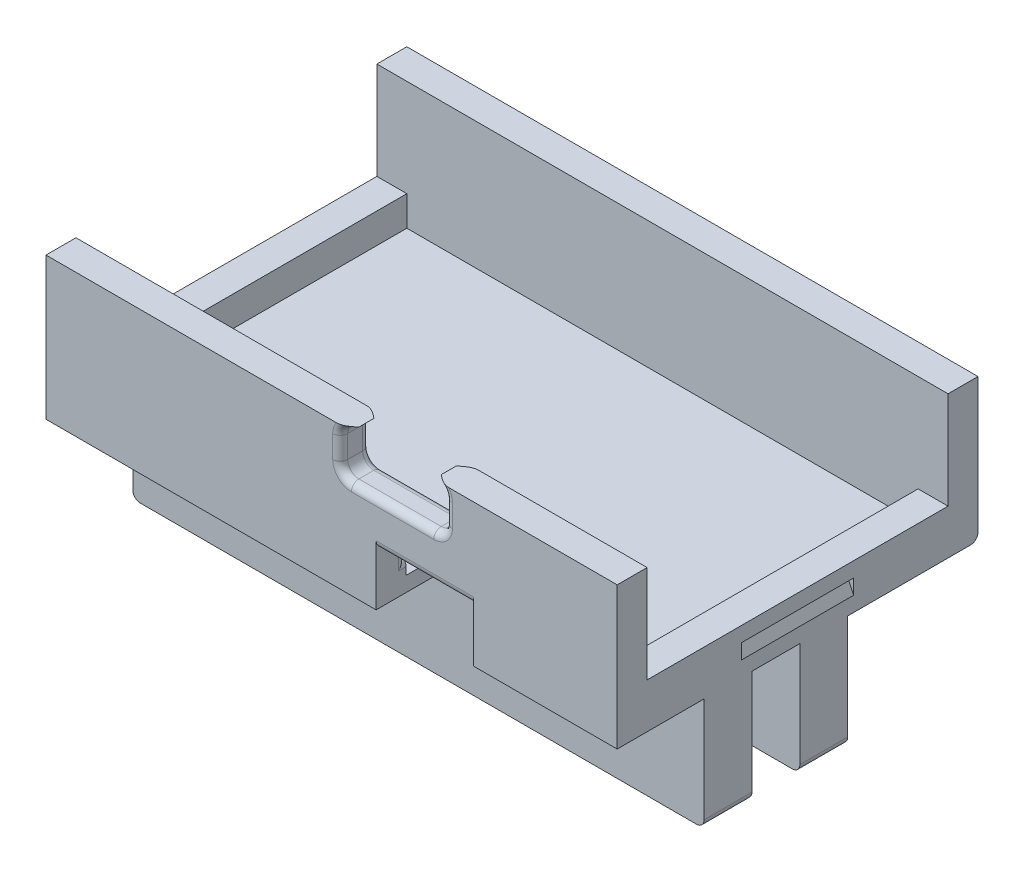
SolidWorks part; units mm, degrees
ref_plane "Alzado" through (0, 0, 0) normal (0, 0, 1) x (1, 0, 0)
ref_plane "Planta" through (0, 0, 0) normal (0, 1, 0) x (1, 0, 0)
ref_plane "Vista lateral" through (0, 0, 0) normal (1, 0, 0) x (0, 0, -1)
sketch "Sketch1" plane through (0, 0, 0) normal (0, 1, 0) x (1, 0, 0)
  line L1 (-34.15, -20.1) -> (34.15, -20.1)
  line L2 (-34.15, -20.1) -> (-34.15, 20.1)
  line L3 (-34.15, 20.1) -> (34.15, 20.1)
  line L4 (34.15, -20.1) -> (34.15, 20.1)
  line L5 (-34.15, -20.1) -> (34.15, 20.1) construction
  line L6 (-34.15, 20.1) -> (34.15, -20.1) construction
  point P0 (0, 0)
  dimension "D1" = 68.3
  dimension "D2" = 40.2
sketch "Sketch2" plane through (0, 0, 0) normal (0, 1, 0) x (1, 0, 0)
  line L8 (-38.15, 24.1) -> (-38.15, -24.1)
  line L9 (-38.15, -24.1) -> (38.15, -24.1)
  line L10 (38.15, -24.1) -> (38.15, 24.1)
  line L11 (38.15, 24.1) -> (-38.15, 24.1)
  line L12 (-38.15, 24.1) -> (-38.15, -24.1)
  line L13 (-38.15, -24.1) -> (38.15, -24.1)
  line L14 (38.15, -24.1) -> (38.15, 24.1)
  line L15 (38.15, 24.1) -> (-38.15, 24.1)
  dimension "D1" = 4
extrude "Boss-Extrude1" add sketch "Sketch2" along normal blind 4
sketch "Sketch3" plane through (0, 4, 0) normal (0, 1, 0) x (1, 0, 0)
  line L4 (-34.15, -20.1) -> (34.15, -20.1) construction
  line L6 (-34.15, 20.1) -> (34.15, 20.1) construction
  line L8 (38.15, 24.1) -> (-38.15, 24.1)
  line L9 (-38.15, 24.1) -> (-38.15, -24.1)
  line L10 (-38.15, -24.1) -> (38.15, -24.1)
  line L11 (38.15, -24.1) -> (38.15, 24.1)
  line L12 (38.15, 24.1) -> (-38.15, 24.1)
  line L14 (-38.15, -24.1) -> (38.15, -24.1)
  line L16 (-34.15, -20.1) -> (34.15, -20.1)
  line L18 (-34.15, 20.1) -> (34.15, 20.1)
  line L20 (-34.15, 20.1) -> (-38.15, 20.1)
  line L21 (-38.15, 24.1) -> (-38.15, -24.1) construction
  line L22 (-38.15, 20.1) -> (-38.15, 24.1)
  line L23 (34.15, 20.1) -> (38.15, 20.1)
  line L24 (38.15, -24.1) -> (38.15, 24.1) construction
  line L25 (38.15, 20.1) -> (38.15, 24.1)
  line L26 (34.15, -20.1) -> (38.15, -20.1)
  line L27 (38.15, -20.1) -> (38.15, -24.1)
  line L28 (-34.15, -20.1) -> (-38.15, -20.1)
  line L29 (-38.15, -20.1) -> (-38.15, -24.1)
  dimension "D1" = 0
extrude "Boss-Extrude2" add sketch "Sketch3" along normal blind 15
sketch "Sketch10" plane through (0, 4, 0) normal (0, 1, 0) x (1, 0, 0)
  line L0 (-38.15, 20.1) -> (-34.15, 20.1)
  line L1 (-34.15, 20.1) -> (-34.15, -20.1)
  line L2 (-34.15, -20.1) -> (-38.15, -20.1)
  line L3 (-38.15, -20.1) -> (-38.15, 20.1)
  line L4 (34.15, 20.1) -> (38.15, 20.1)
  line L5 (38.15, 20.1) -> (38.15, -20.1)
  line L6 (38.15, -20.1) -> (34.15, -20.1)
  line L7 (34.15, -20.1) -> (34.15, 20.1)
extrude "Boss-Extrude5" add sketch "Sketch10" along normal blind 2
sketch "Sketch5" plane through (0, 4, 0) normal (0, 1, 0) x (1, 0, 0)
  line L1 (18.95, -12.9) -> (18.95, -24.1)
  line L3 (-38.15, -24.1) -> (38.15, -24.1) construction
  line L4 (18.95, -24.1) -> (5.95, -24.1)
  line L5 (5.95, -24.1) -> (5.95, -12.9)
  line L6 (5.95, -12.9) -> (18.95, -12.9)
  line L7 (34.15, -20.1) -> (34.15, 20.1) construction
  line L8 (-34.15, -20.1) -> (34.15, -20.1) construction
  dimension "D1" = 15.2
  dimension "D2" = 13
  dimension "D3" = 7.2
extrude "Cut-Extrude1" cut sketch "Sketch5" against normal blind 4 and the other way blind 3
sketch "Sketch7" plane through (38.15, 0, 0) normal (1, 0, 0) x (0, 0, -1)
  line L0 (-20.1, 12.5) -> (-20.1, 17)
  line L2 (-20.1, 12.5) -> (-17.1, 17)
  line L3 (-17.1, 17) -> (-20.1, 17)
  line L4 (-20.1, 19) -> (-20.1, 6) construction
  line L5 (-20.1, 4) -> (20.1, 4) construction
  dimension "D1" = 3
  dimension "D2" = 13
  dimension "D3" = 4.5
sketch "Sketch8" plane through (0, 0, 24.1) normal (0, 0, 1) x (1, 0, 0)
  line L0 (2.65, 19) -> (13.65, 19)
  line L2 (15.15, 17.5) -> (15.15, 14.5)
  line L3 (13.65, 13) -> (2.65, 13)
  line L4 (1.15, 14.5) -> (1.15, 17.5)
  line L7 (5.95, 4) -> (18.95, 4) construction
  arc A0 (13.65, 19) -> (15.15, 17.5) centre (13.65, 17.5) cw
  arc A1 (15.15, 14.5) -> (13.65, 13) centre (13.65, 14.5) cw
  arc A2 (2.65, 13) -> (1.15, 14.5) centre (2.65, 14.5) cw
  arc A3 (1.15, 17.5) -> (2.65, 19) centre (2.65, 17.5) cw
  dimension "D1" = 6
  dimension "D4" = 1.5
  dimension "D2" = 15
  dimension "D3" = 14
  dimension "D5" = 19
extrude "Cut-Extrude2" cut sketch "Sketch8" against normal up to next
sketch "Sketch14" plane through (38.15, 0, 0) normal (1, 0, 0) x (0, 0, -1)
  line L0 (-20.1, 6) -> (20.1, 6) construction
  line L2 (-20.1, 19) -> (-20.1, 6) construction
  point P3 (0, 6)
sketch "Sketch13" plane through (0, 0, 0) normal (0, 0, 1) x (1, 0, 0)
  line L0 (38.15, 0) -> (38.15, 6) construction
  line L2 (38.15, 4) -> (37.15, 4)
  line L3 (37.15, 4) -> (38.15, 2)
  line L4 (38.15, 4) -> (38.15, 2) construction
  line L5 (38.15, 4) -> (38.15, 2)
  point P9 (38.15, 3)
  point P13 (38.15, 3)
  dimension "D1" = 1
  dimension "D2" = 2
extrude "Cut-Extrude3" cut sketch "Sketch13" against normal mid plane 15
mirror "Mirror2" about plane through (0, 0, 0) normal (1, 0, 0) of "Cut-Extrude3"
fillet "Fillet3" radius 1 1 edges at (0, 0, -24.1)
sketch "Sketch17" plane through (0, 0, 0) normal (0, -1, 0) x (1, 0, 0)
  line L0 (38.15, 20.1) -> (38.15, -20.1) construction
  line L1 (-38.15, 24.1) -> (38.15, 24.1)
  line L2 (-38.15, 24.1) -> (-38.15, 16.1)
  line L3 (-38.15, 16.1) -> (38.15, 16.1)
  line L4 (38.15, 24.1) -> (38.15, 16.1)
  line L5 (-38.15, 24.1) -> (38.15, 16.1) construction
  line L6 (-38.15, 16.1) -> (38.15, 24.1) construction
  line L7 (-38.15, -23.1) -> (-38.15, 24.1) construction
  line L8 (-38.15, 9.7) -> (38.15, 9.7)
  line L9 (-38.15, 9.7) -> (-38.15, 3.7)
  line L10 (-38.15, 3.7) -> (38.15, 3.7)
  line L11 (38.15, 9.7) -> (38.15, 3.7)
  line L12 (-38.15, 9.7) -> (38.15, 3.7) construction
  line L13 (-38.15, 3.7) -> (38.15, 9.7) construction
  line L14 (38.15, 24.1) -> (38.15, -23.1) construction
  point P4 (0, 20.1)
  point P12 (0, 6.7)
  dimension "D1" = 8
  dimension "D2" = 6
  dimension "D3" = 6.4
extrude "Boss-Extrude6" add sketch "Sketch17" along normal blind 15
ref_plane "Plane1" through (0, 0, 0) normal (0, -1, 0) x (-1, 0, 0)
sketch "Sketch20" plane through (0, 0, 24.1) normal (0, 0, 1) x (1, 0, 0)
  line L0 (0, 0) -> (0, -15) construction
  line L1 (18.95, 7) -> (18.95, 0) construction
  line L2 (38.15, -15) -> (-38.15, -15) construction
  line L3 (-3.575, 0) -> (3.575, 0) construction
  circle A0 centre (23.95, -9) radius 2.55
  circle A1 centre (-23.95, -9) radius 2.55
  point P8 (18.95, 3.5)
  dimension "D1" = 5.1
  dimension "D2" = 6.45
  dimension "D3" = 5
extrude "Cut-Extrude5" cut sketch "Sketch20" against normal through all
fillet "Fillet4" radius 1 4 edges at (-38.15, -15, 6.7) (-38.15, -15, 20.1) (38.15, -15, 6.7) (38.15, -15, 20.1)
fillet "Fillet5" radius 1 21 edges at (12.45, 4, 12.9) (5.95, 4, 16.5) (18.95, 4, 16.5) (18.95, 5.5, 20.1) (5.95, 5.5, 20.1) (12.45, 7, 20.1) (12.45, 7, 24.1) (1.5893, 18.5607, 24.1) (14.7107, 18.5607, 24.1) (15.15, 16, 24.1) (14.7107, 13.4393, 24.1) (8.15, 13, 24.1) (1.5893, 13.4393, 24.1) (14.7107, 13.4393, 20.1) (15.15, 16, 20.1) (14.7107, 18.5607, 20.1) (1.5893, 18.5607, 20.1) (1.15, 16, 20.1) (1.5893, 13.4393, 20.1) (1.15, 16, 24.1) (8.15, 13, 20.1)
sketch "Sketch21" plane through (0, 4, 0) normal (0, 1, 0) x (1, 0, 0)
  line L1 (-34.15, 20.1) -> (34.15, 20.1)
  line L2 (-34.15, 20.1) -> (-34.15, -20.1)
  line L3 (-34.15, -20.1) -> (34.15, -20.1)
  line L4 (34.15, 20.1) -> (34.15, -20.1)
  line L5 (-34.15, 20.1) -> (34.15, -20.1) construction
  line L6 (-34.15, -20.1) -> (34.15, 20.1) construction
  point P4 (0, 0)
extrude "Cut-Extrude6" cut sketch "Sketch21" against normal blind 2
ref_plane "Plane2" through (0, 0, 34.1) normal (0, 0, 1) x (1, 0, 0)
mirror "Mirror4" [suppressed] about plane through (0, 0, 34.1) normal (0, 0, 1) of bodies 114
sketch "Sketch22" [suppressed] plane through (0, 0, 34.1) normal (0, 0, 1) x (1, 0, 0)
  line L0 (-37.15, -15) -> (37.15, -15) construction
  line L1 (-38.15, 19) -> (38.15, 19)
  line L2 (-38.15, 19) -> (-38.15, -15)
  line L3 (-38.15, -15) -> (38.15, -15)
  line L4 (38.15, 19) -> (38.15, -15)
  line L5 (-38.15, 19) -> (38.15, -15) construction
  line L6 (-38.15, -15) -> (38.15, 19) construction
  line L7 (38.15, -14) -> (38.15, 0) construction
  point P4 (0, 2)
extrude "Cut-Extrude7" [suppressed] cut sketch "Sketch22" against normal through all
sketch "Sketch23" [suppressed] plane through (0, 0, 24.1) normal (0, 0, 1) x (1, 0, 0)
  line L0 (-35.55, 0) -> (35.55, 0) construction
  line L1 (-3.575, 0) -> (3.575, 0) construction
  line L3 (-35.55, 0) -> (-41.9, 0)
  line L4 (-35.55, 0) -> (-35.55, -14)
  line L5 (-35.55, -14) -> (-41.9, -14)
  line L6 (-41.9, 0) -> (-41.9, -14)
  line L7 (-35.55, 0) -> (-41.9, -14) construction
  line L8 (-35.55, -14) -> (-41.9, 0) construction
  line L9 (35.55, 0) -> (41.9, 0)
  line L10 (35.55, 0) -> (35.55, -14)
  line L11 (35.55, -14) -> (41.9, -14)
  line L12 (41.9, 0) -> (41.9, -14)
  line L13 (35.55, 0) -> (41.9, -14) construction
  line L14 (35.55, -14) -> (41.9, 0) construction
  line L15 (29.05, 0) -> (22.7, 0)
  line L16 (29.05, 0) -> (29.05, -14)
  line L17 (29.05, -14) -> (22.7, -14)
  line L18 (22.7, 0) -> (22.7, -14)
  line L19 (29.05, 0) -> (22.7, -14) construction
  line L20 (29.05, -14) -> (22.7, 0) construction
  line L21 (-22.7, 0) -> (-29.05, 0)
  line L22 (-22.7, 0) -> (-22.7, -14)
  line L23 (-22.7, -14) -> (-29.05, -14)
  line L24 (-29.05, 0) -> (-29.05, -14)
  line L25 (-22.7, 0) -> (-29.05, -14) construction
  line L26 (-22.7, -14) -> (-29.05, 0) construction
  point P6 (0, 0)
  point P10 (-38.725, -7)
  point P14 (38.725, -7)
  point P19 (25.875, -7)
  point P24 (-25.875, -7)
  dimension "D1" = 71.1
  dimension "D2" = 6.35
  dimension "D3" = 14
  dimension "D4" = 6.5
  dimension "D5" = 6.5
  dimension "D6" = 6.35
extrude "Boss-Extrude7" [suppressed] add sketch "Sketch23" against normal through all
sketch "Sketch24" [suppressed] plane through (0, 0, 64.5) normal (0, 0, 1) x (1, 0, 0)
  line L4 (-37.15, -15) -> (37.15, -15)
  line L5 (38.15, -14) -> (38.15, 0)
  line L6 (38.15, 0) -> (-38.15, 0)
  line L7 (-38.15, 0) -> (-38.15, -14)
  line L8 (-37.15, -15) -> (37.15, -15)
  line L9 (38.15, -14) -> (38.15, 0)
  line L10 (38.15, 0) -> (-38.15, 0)
  line L11 (-38.15, 0) -> (-38.15, -14)
  circle A0 centre (22.95, -9) radius 2.55 construction
  circle A1 centre (22.95, -9) radius 2.55
  arc A2 (37.15, -15) -> (38.15, -14) centre (37.15, -14) ccw
  arc A3 (-38.15, -14) -> (-37.15, -15) centre (-37.15, -14) ccw
  arc A4 (37.15, -15) -> (38.15, -14) centre (37.15, -14) ccw
  arc A5 (-38.15, -14) -> (-37.15, -15) centre (-37.15, -14) ccw
  dimension "D1" = 0
extrude "Boss-Extrude8" [suppressed] add sketch "Sketch24" along normal blind 10 and the other way blind 15
sketch "Sketch25" [suppressed] plane through (0, 0, 74.5) normal (0, 0, 1) x (1, 0, 0)
  line L4 (-37.15, -15) -> (37.15, -15)
  line L5 (38.15, -14) -> (38.15, 0)
  line L6 (38.15, 0) -> (-38.15, 0)
  line L7 (-38.15, 0) -> (-38.15, -14)
  line L8 (-37.15, -15) -> (37.15, -15)
  line L9 (38.15, -14) -> (38.15, 0)
  line L10 (38.15, 0) -> (-38.15, 0)
  line L11 (-38.15, 0) -> (-38.15, -14)
  circle A0 centre (22.95, -9) radius 2.55 construction
  circle A1 centre (22.95, -9) radius 2.55
  arc A2 (-38.15, -14) -> (-37.15, -15) centre (-37.15, -14) ccw
  arc A3 (37.15, -15) -> (38.15, -14) centre (37.15, -14) ccw
  arc A4 (-38.15, -14) -> (-37.15, -15) centre (-37.15, -14) ccw
  arc A5 (37.15, -15) -> (38.15, -14) centre (37.15, -14) ccw
  dimension "D1" = 0
extrude "Cut-Extrude10" [suppressed] cut sketch "Sketch25" against normal blind 6.4 from offset 6.35 offset against normal yes
sketch "Sketch27" [suppressed] plane through (0, 0, 61.75) normal (0, 0, 1) x (1, 0, 0)
  line L4 (-37.15, -15) -> (37.15, -15)
  line L5 (38.15, -14) -> (38.15, 0)
  line L6 (38.15, 0) -> (-38.15, 0)
  line L7 (-38.15, 0) -> (-38.15, -14)
  line L8 (-37.15, -15) -> (37.15, -15)
  line L9 (38.15, -14) -> (38.15, 0)
  line L10 (38.15, 0) -> (-38.15, 0)
  line L11 (-38.15, 0) -> (-38.15, -14)
  circle A0 centre (22.95, -9) radius 2.55 construction
  circle A1 centre (22.95, -9) radius 2.55
  arc A2 (-38.15, -14) -> (-37.15, -15) centre (-37.15, -14) ccw
  arc A3 (37.15, -15) -> (38.15, -14) centre (37.15, -14) ccw
  arc A4 (-38.15, -14) -> (-37.15, -15) centre (-37.15, -14) ccw
  arc A5 (37.15, -15) -> (38.15, -14) centre (37.15, -14) ccw
  dimension "D1" = 0
extrude "Cut-Extrude11" [suppressed] cut sketch "Sketch27" against normal through all from offset 6.35 offset against normal yes
sketch "Sketch28" [suppressed] plane through (-41.9, 0, 0) normal (-1, 0, 0) x (0, 0, 1)
  line L0 (-24.1, 0) -> (24.1, 0) construction
  circle A0 centre (-18.1419, -9.05) radius 2.6
  dimension "D1" = 6.45
  dimension "D2" = 5.2
sketch "Sketch29" plane through (0, 0, 16.1) normal (0, 0, -1) x (-1, 0, 0)
  line L6 (-37.15, -15) -> (37.15, -15)
  line L7 (38.15, -14) -> (38.15, 0)
  line L8 (38.15, 0) -> (-5.95, 0)
  line L9 (-5.95, 0) -> (-18.95, 0)
  line L10 (-18.95, 0) -> (-38.15, 0)
  line L11 (-38.15, 0) -> (-38.15, -14)
  line L12 (-37.15, -15) -> (37.15, -15)
  line L13 (38.15, -14) -> (38.15, 0)
  line L14 (38.15, 0) -> (-5.95, 0)
  line L15 (-5.95, 0) -> (-18.95, 0)
  line L16 (-18.95, 0) -> (-38.15, 0)
  line L17 (-38.15, 0) -> (-38.15, -14)
  circle A0 centre (-23.95, -9) radius 2.55 construction
  circle A1 centre (-23.95, -9) radius 2.55
  arc A2 (37.15, -15) -> (38.15, -14) centre (37.15, -14) ccw
  arc A3 (-38.15, -14) -> (-37.15, -15) centre (-37.15, -14) ccw
  arc A4 (37.15, -15) -> (38.15, -14) centre (37.15, -14) ccw
  arc A5 (-38.15, -14) -> (-37.15, -15) centre (-37.15, -14) ccw
  circle A6 centre (23.95, -9) radius 2.55 construction
  circle A7 centre (23.95, -9) radius 2.55
  dimension "D1" = 0
extrude "Boss-Extrude9" add sketch "Sketch29" along normal through all
sketch "Sketch30" plane through (38.15, 0, 0) normal (1, 0, 0) x (0, 0, -1)
  line L0 (24.1, -15) -> (-24.1, -15) construction
  line L1 (24.1, 0) -> (6.7, 0)
  line L2 (24.1, 0) -> (24.1, -15)
  line L3 (24.1, -15) -> (6.7, -15)
  line L4 (6.7, 0) -> (6.7, -15)
  line L5 (24.1, 0) -> (6.7, -15) construction
  line L6 (24.1, -15) -> (6.7, 0) construction
  line L8 (-24.1, -15) -> (-12.5, -15)
  line L9 (-24.1, -15) -> (-24.1, 0)
  line L10 (-24.1, 0) -> (-12.5, 0)
  line L11 (-12.5, -15) -> (-12.5, 0)
  line L12 (-24.1, -15) -> (-12.5, 0) construction
  line L13 (-24.1, 0) -> (-12.5, -15) construction
  line L14 (0.3, -15) -> (-6.1, -15)
  line L15 (0.3, -15) -> (0.3, 0)
  line L16 (0.3, 0) -> (-6.1, 0)
  line L17 (-6.1, -15) -> (-6.1, 0)
  line L18 (0.3, -15) -> (-6.1, 0) construction
  line L19 (0.3, 0) -> (-6.1, -15) construction
  point P4 (15.4, -7.5)
  point P12 (-18.3, -7.5)
  point P19 (-2.9, -7.5)
  dimension "D1" = 11.6
  dimension "D2" = 6.4
  dimension "D3" = 6.4
  dimension "D4" = 6.4
extrude "Cut-Extrude12" cut sketch "Sketch30" against normal through all
